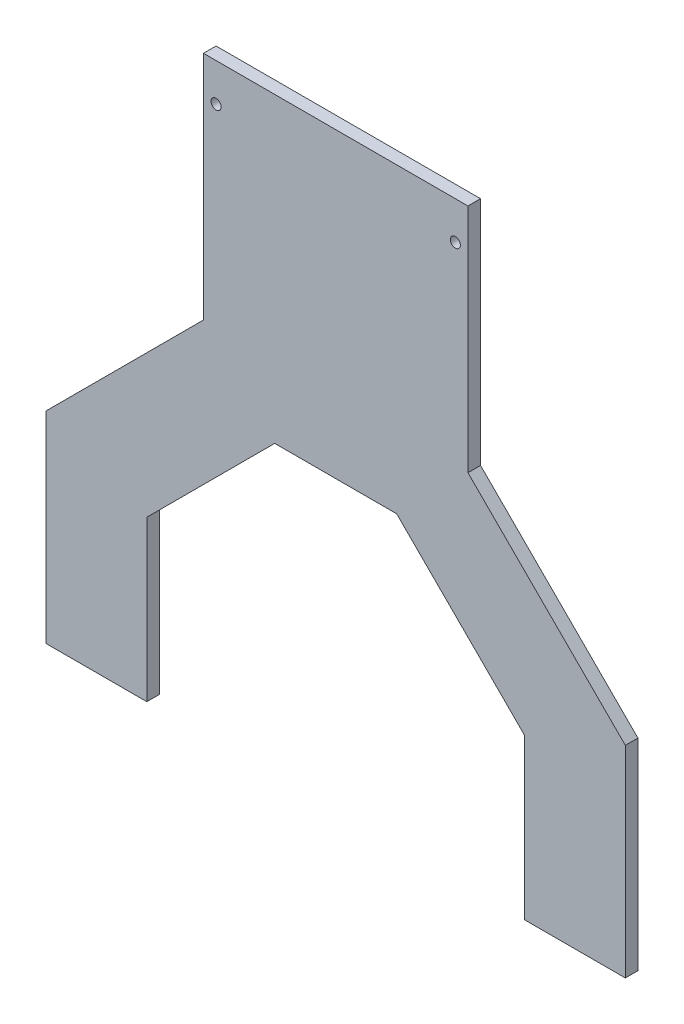
SolidWorks part; units mm, degrees
ref_plane "Front Plane" through (0, 0, 0) normal (0, 0, 1) x (1, 0, 0)
ref_plane "Top Plane" through (0, 0, 0) normal (0, 1, 0) x (1, 0, 0)
ref_plane "Right Plane" through (0, 0, 0) normal (1, 0, 0) x (0, 0, -1)
sketch "Sketch1" plane through (0, 0, 0) normal (0, 0, 1) x (1, 0, 0)
  line L1 (-100, -75) -> (100, -75)
  line L2 (-100, -75) -> (-100, 75)
  line L3 (-100, 75) -> (100, 75)
  line L4 (100, -75) -> (100, 75)
  line L5 (-100, -75) -> (100, 75) construction
  line L6 (-100, 75) -> (100, -75) construction
  line L8 (-47.5, 45) -> (47.5, 45) construction
  line L9 (0, 75) -> (0, -75) construction
  line L10 (-27, -39) -> (27, -39) construction
  line L11 (-27, -39) -> (-27, 33) construction
  line L12 (-27, 33) -> (27, 33) construction
  line L13 (27, -39) -> (27, 33) construction
  line L14 (-27, -39) -> (27, 33) construction
  line L15 (-27, 33) -> (27, -39) construction
  line L23 (-52.5, 60) -> (52.5, 60)
  line L24 (-52.5, 60) -> (-52.5, -60)
  line L25 (-52.5, -60) -> (52.5, -60)
  line L26 (52.5, 60) -> (52.5, -60)
  line L27 (-52.5, 60) -> (52.5, -60) construction
  line L28 (-52.5, -60) -> (52.5, 60) construction
  line L29 (-32.5, 60) -> (32.5, 60) construction
  line L30 (-32.5, 60) -> (-32.5, 45) construction
  line L31 (-32.5, 45) -> (32.5, 45) construction
  line L32 (32.5, 60) -> (32.5, 45) construction
  line L33 (-32.5, 60) -> (32.5, 45) construction
  line L34 (-32.5, 45) -> (32.5, 60) construction
  circle A2 centre (-47.5, 45) radius 2
  circle A3 centre (47.5, 45) radius 2
  circle A4 centre (-27, 33) radius 2 construction
  circle A5 centre (27, 33) radius 2 construction
  circle A6 centre (27, -39) radius 2 construction
  circle A7 centre (-27, -39) radius 2 construction
  point P0 (0, 0)
  point P15 (0, 45)
  point P18 (0, -3)
  point P56 (0, 0)
  point P63 (0, 52.5)
  dimension "D5" = 4
  dimension "D8" = 4
  dimension "D1" = 150
  dimension "D2" = 200
  dimension "D6" = 72
  dimension "D7" = 54
  dimension "D14" = 15
  dimension "D15" = 120
  dimension "D16" = 105
  dimension "D17" = 95
  dimension "D18" = 12
  dimension "D19" = 15
  dimension "D20" = 65
extrude "Boss-Extrude1" add sketch "Sketch1" along normal blind 5 contours L23 L32 L31 L30 L24 L25 L26 A7 A6 A5 A4 A3 A2 region at (0, -0.0899, 0)
sketch "Sketch2" plane through (0, 0, 0) normal (0, 0, 1) x (1, 0, 0)
  line L0 (-52.5, -60) -> (-100.8579, -108.3579) construction
  line L1 (-52.5, 60) -> (-52.5, -60) construction
  line L2 (-52.5, -31.7157) -> (-115, -94.2157)
  line L3 (-24.2157, -60) -> (-86.7157, -122.5)
  line L4 (-52.5, -60) -> (52.5, -60) construction
  line L5 (-115, -94.2157) -> (-86.7157, -122.5)
  line L6 (-115, -94.2157) -> (-115, -174.2157)
  line L7 (-75, -110.7843) -> (-75, -174.2157)
  line L8 (-75, -174.2157) -> (-115, -174.2157)
  line L9 (0, 75) -> (0, -75) construction
  line L10 (-52.5, -31.7157) -> (-24.2157, -60)
  line L11 (-52.5, 60) -> (-52.5, -60) construction
  dimension "D1" = 135
  dimension "D2" = 40
  dimension "D3" = 40
  dimension "D4" = 75
  dimension "D5" = 80
extrude "Boss-Extrude2" add sketch "Sketch2" along normal blind 5 contours L8 L7 L3 L5 L6 | L10 L2 L5 L3 region at (-69.6079, -77.1079, 0) region at (-96.2313, -141.99, 0)
mirror "Mirror1" about plane through (0, 0, 0) normal (1, 0, 0) of "Boss-Extrude2"
